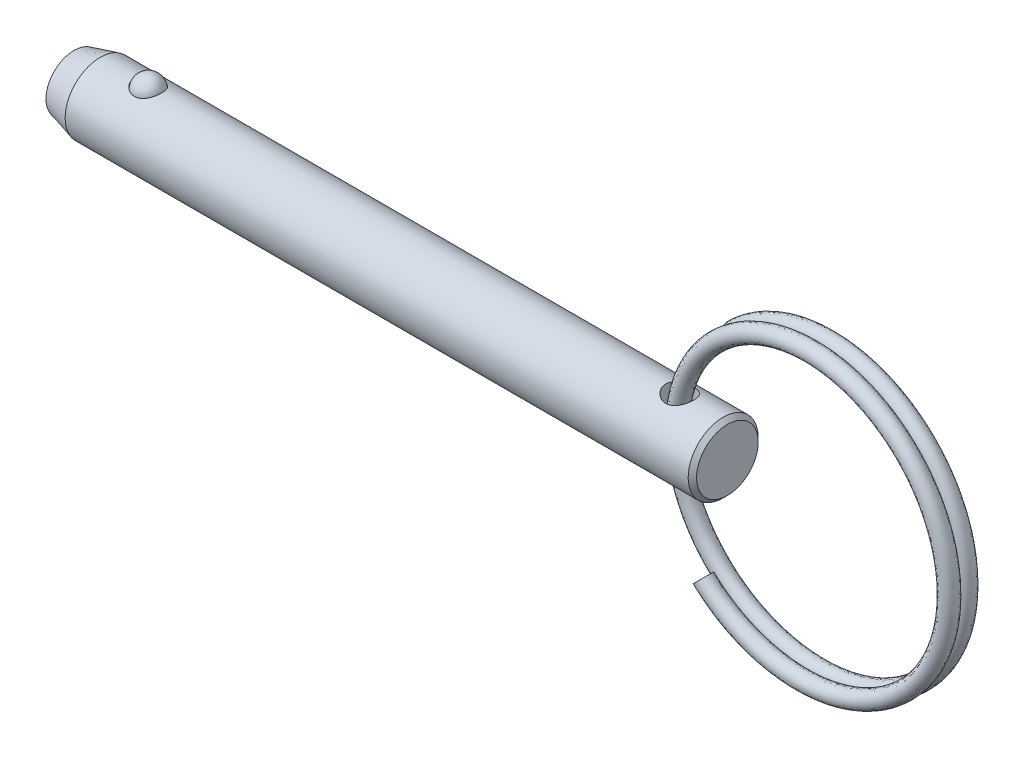
SolidWorks part; units mm, degrees
ref_plane "Front" through (0, 0, 0) normal (0, 0, 1) x (1, 0, 0)
ref_plane "Top" through (0, 0, 0) normal (0, 1, 0) x (1, 0, 0)
ref_plane "Right" through (0, 0, 0) normal (1, 0, 0) x (0, 0, -1)
sketch "Sketch1" plane through (0, 0, 0) normal (0, 0, 1) x (1, 0, 0)
  line L0 (29.6164, 2.794) -> (29.2354, 3.175)
  line L1 (29.2354, 3.175) -> (29.6164, 3.175) construction
  line L4 (29.6164, 2.794) -> (29.6164, 0)
  line L5 (29.6164, 3.175) -> (29.6164, 2.794) construction
  line L16 (29.2354, 3.175) -> (-27.2465, 3.175)
  line L17 (-29.6164, 3.175) -> (-29.6164, 2.54) construction
  line L19 (-27.2465, 3.175) -> (-29.6164, 3.175) construction
  line L22 (-29.6164, -3.175) -> (-27.2465, -3.175) construction
  line L23 (-22.8819, 2.8575) -> (-22.8819, -2.8575) construction
  line L24 (-29.6164, 0) -> (29.6164, 0)
  line L27 (29.6164, 0) -> (32.4104, 0) construction
  line L29 (-29.6164, 0) -> (-29.6164, -2.54) construction
  line L36 (24.0284, 0) -> (24.0284, 3.175) construction
  line L37 (-29.6164, 2.54) -> (-29.6164, 0)
  line L38 (-27.2465, -3.175) -> (29.6164, -3.175) construction
  line L39 (-29.6164, -2.54) -> (-29.6164, -3.175) construction
  line L40 (-27.2465, 3.175) -> (-29.6164, 2.54)
  line L42 (-27.2465, -3.175) -> (-29.6164, -2.54) construction
  line L43 (-27.2465, 3.175) -> (-27.2465, -3.175) construction
  circle A2 centre (-22.8819, 2.8575) radius 1.2319 construction
  point P35 (-21.6916, 3.175)
  dimension "A1" = 15
revolve "Revolve1" add sketch "Sketch1" angle 360 about L27
sketch "Sketch2" plane through (0, 0, 0) normal (0, 0, 1) x (1, 0, 0)
  line L0 (-21.6246, 2.8575) -> (-24.1392, 2.8575)
  line L1 (-22.8819, 4.0894) -> (-22.8819, 4.1148) construction
  line L2 (-21.6246, 2.8575) -> (-19.11, 2.8575) construction
  circle A0 centre (-22.8819, 2.8575) radius 1.2319 construction
  circle A1 centre (-22.8819, 2.8575) radius 1.2319 construction
  arc A2 (-24.1392, 2.8575) -> (-21.6246, 2.8575) centre (-22.8819, 2.8575) cw
  dimension "D1" = 0.0254
revolve "Cut-Revolve1" cut sketch "Sketch2" angle 360 about L2
sketch "Sketch3" plane through (0, 0, 0) normal (0, 0, 1) x (1, 0, 0)
  line L0 (-21.65, 2.8575) -> (-24.1138, 2.8575)
  line L1 (-21.65, 2.8575) -> (-19.1862, 2.8575) construction
  circle A0 centre (-22.8819, 2.8575) radius 1.2319 construction
  arc A1 (-21.65, 2.8575) -> (-24.1138, 2.8575) centre (-22.8819, 2.8575) ccw
revolve "Revolve2" add sketch "Sketch3" angle 360 about L1
sketch "Sketch4" plane through (0, 0, 0) normal (0, 0, 1) x (1, 0, 0)
  line L1 (25.2984, -3.175) -> (26.5684, -3.175)
  line L2 (25.2984, -3.175) -> (25.2984, 3.175)
  line L3 (25.2984, 3.175) -> (26.5684, 3.175)
  line L4 (26.5684, -3.175) -> (26.5684, 3.175)
  line L5 (25.2984, -3.175) -> (25.2984, -4.445) construction
  line L6 (26.5684, 3.175) -> (29.6164, 3.175) construction
  line L8 (24.0284, -3.175) -> (24.0284, 3.175) construction
  line L9 (24.0284, 0) -> (25.2984, 0) construction
  line L11 (25.2984, 0) -> (26.5684, 0) construction
  line L12 (29.2354, 3.175) -> (-27.2465, 3.175) construction
  line L14 (-27.2465, -3.175) -> (29.6164, -3.175) construction
  dimension "D1" = 2.54
revolve "Cut-Revolve2" cut sketch "Sketch4" angle 360 about L2
sketch "Sketch5" plane through (0, 0, 0) normal (0, 0, 1) x (1, 0, 0)
  line L0 (0, 0) -> (24.3214, 0) construction
  line L1 (24.3214, 0) -> (24.3214, 3.175) construction
  line L2 (29.2354, 3.175) -> (-27.2465, 3.175) construction
  line L3 (37.7834, 0) -> (51.2454, 0) construction
  line L4 (26.5684, 3.175) -> (26.2754, 3.175) construction
  line L5 (25.2984, 3.175) -> (26.5684, 3.175) construction
  line L6 (24.7012, 3.175) -> (24.7012, -3.175) construction
  line L7 (24.3214, 3.175) -> (24.0284, 3.175) construction
  line L8 (25.2984, -3.175) -> (26.5684, -3.175) construction
  line L9 (24.7012, -3.175) -> (26.5684, -3.175) construction
  line L10 (24.3214, 0) -> (37.7834, 0) construction
  line L12 (26.2754, 3.175) -> (24.7012, 3.175) construction
  line L13 (37.7834, 11.938) -> (37.7834, 13.462) construction
  circle A0 centre (37.7834, 0) radius 13.462
  circle A1 centre (37.7834, 0) radius 11.938 construction
  circle A2 centre (37.7834, 0) radius 12.7 construction
  point P26 (37.7834, 12.7)
curve "Helix/Spiral1" pitch 1.5494 height 1.3557 radius 13.462 left hand yes centre (37.7834, 0, 0) axis (0, 0, -1) start towards (1, 0, 0)
sketch "Sketch6" plane through (114.0038, 0, 0) normal (0, 1, 0) x (0, 0, -1)
  line L0 (0, 88.1584) -> (0, 88.9204) construction
  line L1 (0, 88.9204) -> (0, 89.6824) construction
  circle A0 centre (0, 88.9204) radius 0.762
  dimension "D1" = 1.524
sketch "Sketch7" plane through (0, 0, 0) normal (0, 0, 1) x (1, 0, 0)
  circle A0 centre (37.7834, 0) radius 13.462 construction
  circle A1 centre (37.7834, 0) radius 13.462
curve "Helix/Spiral2" pitch 1.5494 height 1.3557 radius 13.462 left hand yes centre (37.7834, 0, 0) axis (0, 0, 1) start towards (1, 0, 0)
sweep "Sweep1" add profiles "Sketch6" path "Helix/Spiral1"
sweep "Sweep2" add profiles "Sketch6<2>" path "Helix/Spiral2"
sketch "Sketch6<2>" plane through (114.0038, 0, 0) normal (0, 1, 0) x (0, 0, -1) same geometry as "Sketch6"
equation "\"D12@Sketch1\"=\"A@Sketch1\" * 0.80"
equation "\"D2@Sketch1\"=\"A@Sketch1\" * 0.9"
equation "\"D1@Sketch4\" = \"A@Sketch1\" / 2.5"
equation "\"Ring OD@Sketch5\" = \"R Ring Dia@Sketch5\" * 0.06"
equation "\"D4@Helix/Spiral1\"=\"Ring OD@Sketch5\" + 0.001"
equation "\"D1@Sketch6\"=\"Ring OD@Sketch5\""
equation "\"D4@Helix/Spiral2\" = \"D4@Helix/Spiral1\""
equation "\"D5@Helix/Spiral2\" = \"D5@Helix/Spiral1\""
